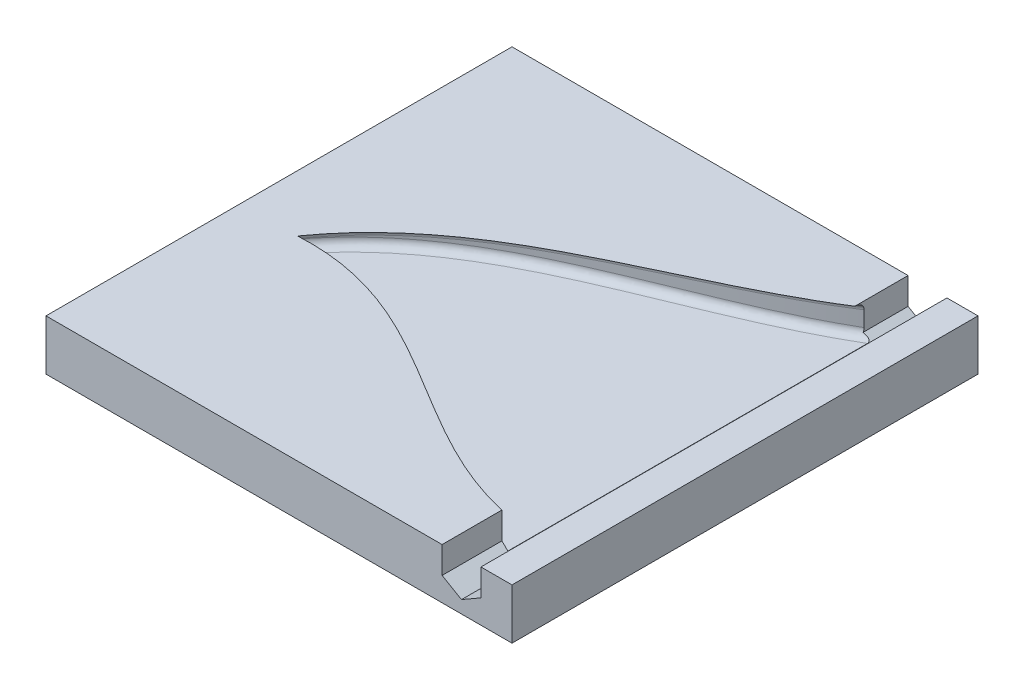
SolidWorks part; units mm, degrees
ref_plane "Front Plane" through (0, 0, 0) normal (0, 0, 1) x (1, 0, 0)
ref_plane "Top Plane" through (0, 0, 0) normal (0, 1, 0) x (1, 0, 0)
ref_plane "Right Plane" through (0, 0, 0) normal (1, 0, 0) x (0, 0, -1)
sketch "Sketch1" plane through (0, 0, 0) normal (0, 1, 0) x (1, 0, 0)
  line L0 (0, 0) -> (0, 120.65)
  line L2 (20.32, 133.35) -> (-132.08, 133.35)
  line L3 (20.32, 133.35) -> (20.32, -19.05)
  line L4 (20.32, -19.05) -> (-132.08, -19.05)
  line L5 (-132.08, 133.35) -> (-132.08, -19.05)
  spline S0 degree 3 poles (-116.84, 44.45) (-89.0536, 85.4398) (-38.7309, 94.4666) (0, 120.65) knots 0 0 0 0 1 1 1 1
  spline S1 degree 3 poles (-116.84, 44.45) (-70.8578, 49.2123) (-42.2379, 7.9461) (0, 0) knots 0 0 0 0 1 1 1 1
  dimension "D1" = 120.65
  dimension "D2" = 116.84
  dimension "D3" = 44.45
  dimension "D4" = 152.4
  dimension "D5" = 152.4
  dimension "D6" = 20.32
  dimension "D7" = 19.05
extrude "Boss-Extrude1" add sketch "Sketch1" along normal blind 12.7
sketch "Sketch2" plane through (0, 0, 0) normal (0, -1, 0) x (1, 0, 0)
  line L1 (-132.08, 19.05) -> (20.32, 19.05)
  line L2 (-132.08, 19.05) -> (-132.08, -133.35)
  line L3 (-132.08, -133.35) -> (20.32, -133.35)
  line L4 (20.32, 19.05) -> (20.32, -133.35)
extrude "Boss-Extrude2" add sketch "Sketch2" along normal blind 6.35
ref_plane "Plane2" through (0, 0, 0) normal (0, 0, 1) x (0, -1, 0)
sketch "Sketch3" plane through (0, 0, 0) normal (0, 0, 1) x (0, -1, 0)
  line L0 (0, 0) -> (0, -116.84)
  line L1 (0, -116.84) -> (-5.08, -116.84)
  line L2 (-5.08, -116.84) -> (0, 0)
  line L3 (-12.7, -132.08) -> (-12.7, 20.32) construction
  line L4 (-12.7, 20.32) -> (6.35, 20.32) construction
  dimension "D1" = 116.84
  dimension "D2" = 12.7
  dimension "D3" = 5.08
  dimension "D4" = 20.32
extrude "Boss-Extrude3" add sketch "Sketch3" against normal through all contours L0 L1 L2
sketch "Sketch4" plane through (0, 12.7, 0) normal (0, 1, 0) x (1, 0, 0)
  line L1 (-132.08, 133.35) -> (20.32, 133.35)
  line L2 (-132.08, 133.35) -> (-132.08, -19.05)
  line L3 (-132.08, -19.05) -> (20.32, -19.05)
  line L4 (20.32, 133.35) -> (20.32, -19.05)
extrude "Cut-Extrude1" cut sketch "Sketch4" against normal blind 2.54
sketch "Sketch5" plane through (0, 0, 0) normal (0, 0, 1) x (0, -1, 0)
  line L0 (-10.16, -132.08) -> (-10.16, 20.32) construction
  line L1 (-1.4138, -2.54) -> (2.2523, 3.81)
  line L2 (2.2523, 3.81) -> (-1.4138, 10.16)
  line L3 (-1.4138, 10.16) -> (-8.7462, 10.16)
  line L4 (-8.7462, 10.16) -> (-12.4123, 3.81)
  line L5 (-12.4123, 3.81) -> (-8.7462, -2.54)
  line L6 (-8.7462, -2.54) -> (-1.4138, -2.54)
  circle A0 centre (-5.08, 3.81) radius 6.35 construction
  dimension "D1" = 12.7
  dimension "D2" = 2.54
  dimension "D3" = 1.4138
extrude "Cut-Extrude3" cut sketch "Sketch5" against normal through all both and the other way through all
fillet "Fillet2" radius 2.54 1 edges at (-89.3759, 3.8859, -72.1353)
sketch "Sketch6" plane through (0, 10.16, 0) normal (0, 1, 0) x (1, 0, 0)
  line L1 (-132.08, 133.35) -> (20.32, 133.35)
  line L2 (-132.08, 133.35) -> (-132.08, -19.05)
  line L3 (-132.08, -19.05) -> (20.32, -19.05)
  line L4 (20.32, 133.35) -> (20.32, -19.05)
extrude "Boss-Extrude4" add sketch "Sketch6" along normal blind 2.54
fillet "Fillet4" radius 2.54 1 edges
sketch "Sketch7" plane through (0, 12.7, 0) normal (0, 1, 0) x (1, 0, 0)
  line L1 (-132.08, 133.35) -> (20.32, 133.35)
  line L2 (-132.08, 133.35) -> (-132.08, -19.05)
  line L3 (-132.08, -19.05) -> (20.32, -19.05)
  line L4 (20.32, 133.35) -> (20.32, -19.05)
extrude "Cut-Extrude4" cut sketch "Sketch7" against normal blind 2.54
sketch "Sketch8" plane through (-2.54, 0, 0) normal (1, 0, 0) x (0, 0, -1)
  line L0 (-19.05, 8.7462) -> (-19.05, 1.4138) construction
  line L1 (-19.05, 5.08) -> (133.35, 5.08)
  line L2 (-19.05, 5.08) -> (-19.05, 14.7392)
  line L3 (-19.05, 14.7392) -> (133.35, 14.7392)
  line L4 (133.35, 5.08) -> (133.35, 14.7392)
  dimension "D1" = 152.4
extrude "Cut-Extrude5" cut sketch "Sketch8" along normal blind 12.7
